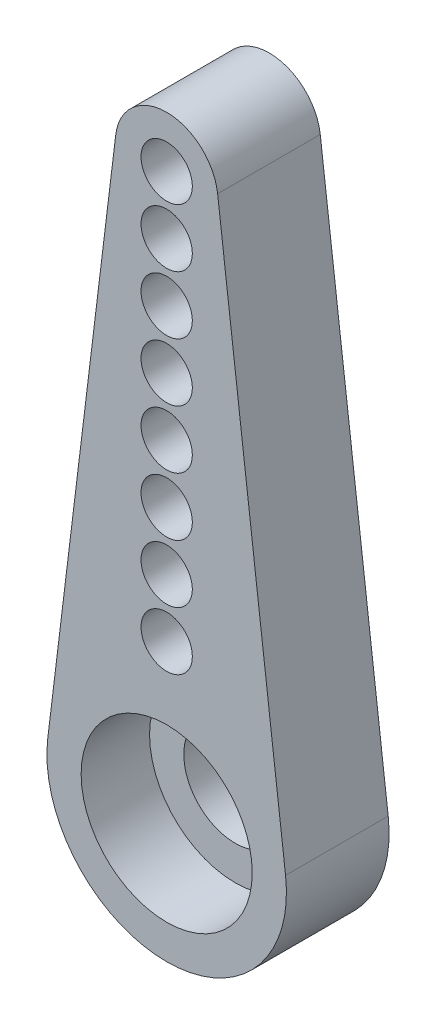
SolidWorks part; units mm, degrees
note: The reader was unsure of these and kept them because the rebuilt part matched: shared geometry of "Sketch2<3>".
ref_plane "Front Plane" through (0, 0, 0) normal (1, 0, 0) x (0, 1, 0)
ref_plane "Top Plane" through (0, 0, 0) normal (0, 0, 1) x (0, 1, 0)
ref_plane "Right Plane" through (0, 0, 0) normal (0, 1, 0) x (-1, 0, 0)
sketch "Sketch2" plane through (0, 0, 0) normal (0, 0, 1) x (0, 1, 0)
  line L0 (0.4242, 3.4742) -> (16.6818, 1.4889)
  line L1 (16.6818, -1.4889) -> (0.4242, -3.4742)
  line L2 (-1000, 0) -> (49000, 0) construction
  circle A0 centre (0, 0) radius 2.5
  arc A1 (0.4242, 3.4742) -> (0.4242, -3.4742) centre (0, 0) ccw
  arc A2 (16.6818, -1.4889) -> (16.6818, 1.4889) centre (16.5, 0) ccw
  circle A3 centre (16.5, 0) radius 0.75
  circle A4 centre (14.8, 0) radius 0.75
  circle A5 centre (13.1, 0) radius 0.75
  circle A6 centre (11.4, 0) radius 0.75
  circle A7 centre (9.7, 0) radius 0.75
  circle A8 centre (8, 0) radius 0.75
  circle A9 centre (6.3, 0) radius 0.75
  circle A10 centre (4.6, 0) radius 0.75
  arc A11 (0.4242, 3.4742) -> (0.4242, -3.4742) centre (0, 0) cw
  circle A12 centre (0, 0) radius 1.5
  point P10 (-3.5, 0)
  point P11 (18, 0)
  dimension "D1" = 5
  dimension "D3" = 1
  dimension "D4" = 3
  dimension "D5" = 1.5
  dimension "D8" = 1
  dimension "D2" = 21.5
  dimension "D7" = 1.7
  dimension "D6" = 8
extrude "Boss-Extrude1" add sketch "Sketch2" along normal blind 1 contours L2 A1 A11 A10 A0 | A1 L2 A0 A10 A11 | A10 L2 A9 A8 A7 A6 A5 A4 A3 A2 L0 A11 | L2 A10 A11 L1 A2 A3 A4 A5 A6 A7 A8 A9 | A0 L2 A12 | L2 A0 A12 | L2 A1 A11 A0 | A1 L2 A0 A11
extrude "Boss-Extrude2" add sketch "Sketch2<3>" along normal blind 3 contours A1 L2 A0 A10 A11 | L2 A1 A11 A10 A0 | L2 A1 A11 A0 | A1 L2 A0 A11
sketch "Sketch2<3>" plane through (0, 0, 0) normal (0, 0, 1) x (0, 1, 0) same geometry as "Sketch2"
